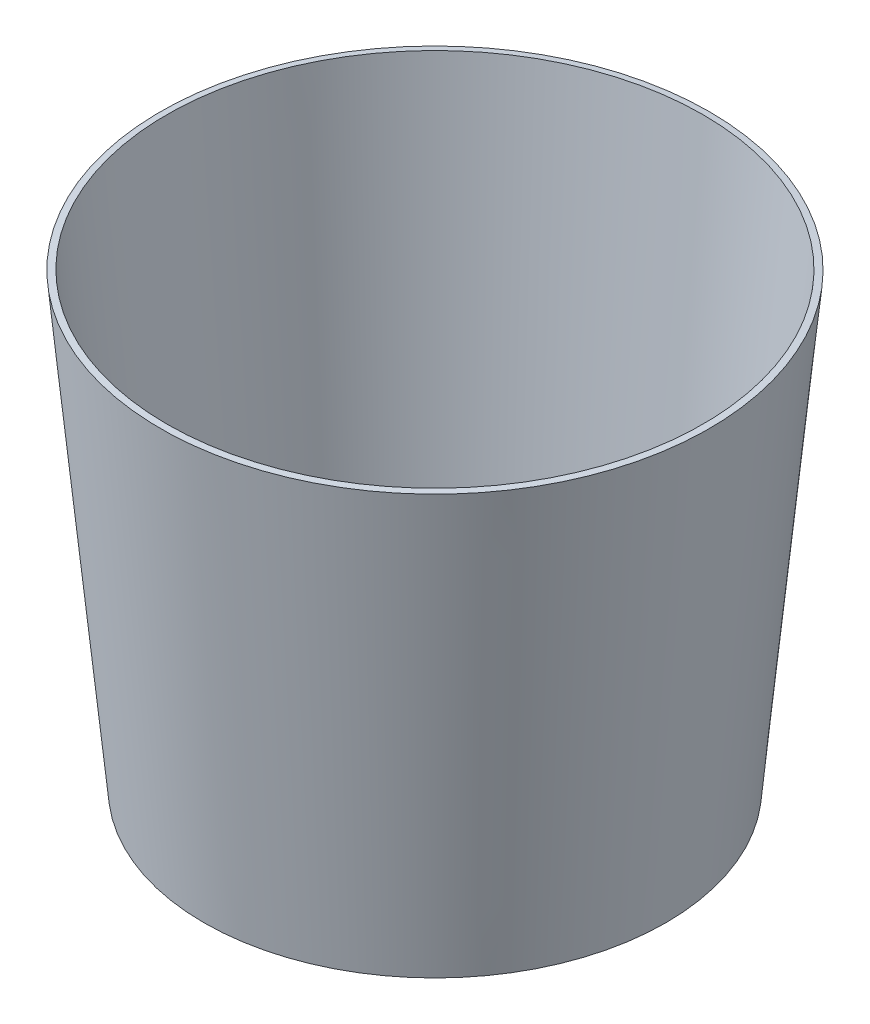
SolidWorks part; units mm, degrees
ref_plane "前基準面" through (0, 0, 0) normal (0, 0, 1) x (1, 0, 0)
ref_plane "上基準面" through (0, 0, 0) normal (0, 1, 0) x (1, 0, 0)
ref_plane "右基準面" through (0, 0, 0) normal (1, 0, 0) x (0, 0, -1)
sketch "草圖1" plane through (0, 0, 0) normal (0, 0, 1) x (1, 0, 0)
  line L1 (0, 0) -> (107.7241, 0)
  line L2 (0, 0) -> (0, 3)
  line L3 (0, 3) -> (105, 3)
  line L5 (105, 3) -> (125, 210)
  line L6 (107.7241, 0) -> (127.9861, 209.7115)
  line L7 (125, 210) -> (127.9861, 209.7115)
  point P1 (0, 0)
  point P3 (127.9861, 210)
  point P4 (0, 0)
  point P7 (0, 0)
  point P8 (90.996, 63.382)
  point P10 (0, 0)
  point P11 (60.8092, 3)
  point P12 (125, 54.7374)
  point P13 (0, 0)
  point P16 (87.3076, 3)
  point P17 (100.4868, 3)
  point P18 (107.5037, 0)
  dimension "D1" = 105
  dimension "D2" = 125
  dimension "D3" = 3
  dimension "D4" = 3
  dimension "D5" = 210
revolve "旋轉1" add sketch "草圖1" angle 360 about L2
